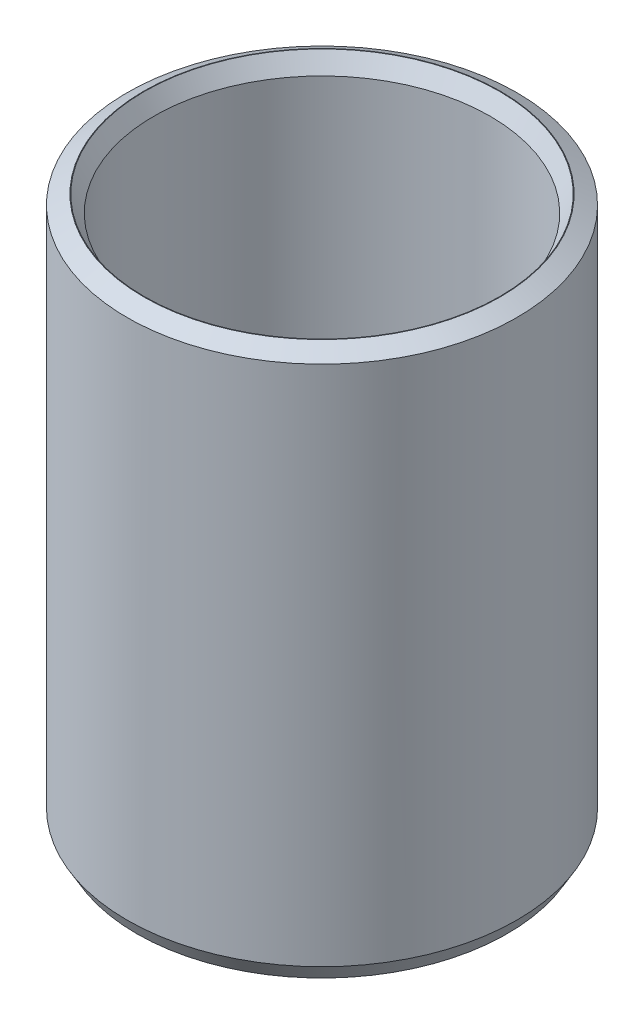
SolidWorks part; units mm, degrees
ref_plane "Front Plane" through (0, 0, 0) normal (0, 0, 1) x (1, 0, 0)
ref_plane "Top Plane" through (0, 0, 0) normal (0, 1, 0) x (1, 0, 0)
ref_plane "Right Plane" through (0, 0, 0) normal (1, 0, 0) x (0, 0, -1)
sketch "Sketch1" plane through (0, 0, 0) normal (0, 1, 0) x (1, 0, 0)
  circle A0 centre (0, 0) radius 47.5
  dimension "SLEEVE_OD" = 95
extrude "Boss-Extrude1" add sketch "Sketch1" along normal blind 133.5829
sketch "Sketch2" plane through (0, 0, 0) normal (0, 1, 0) x (1, 0, 0)
  circle A0 centre (0, 0) radius 40.9785
  dimension "BORE_D" = 81.9571
extrude "Cut-Extrude1" cut sketch "Sketch2" along normal through all
chamfer "Chamfer1" distance 2.3343 angle 60 4 edges at (0, 133.5829, 40.9785) (0, 0, 40.9785) (0, 0, 47.5) (0, 133.5829, 47.5) first distance on face at (0, 133.5829, 40.9785) first distance on face at (0, 0, 40.9785) first distance on face at (0, 133.5829, 47.5)
